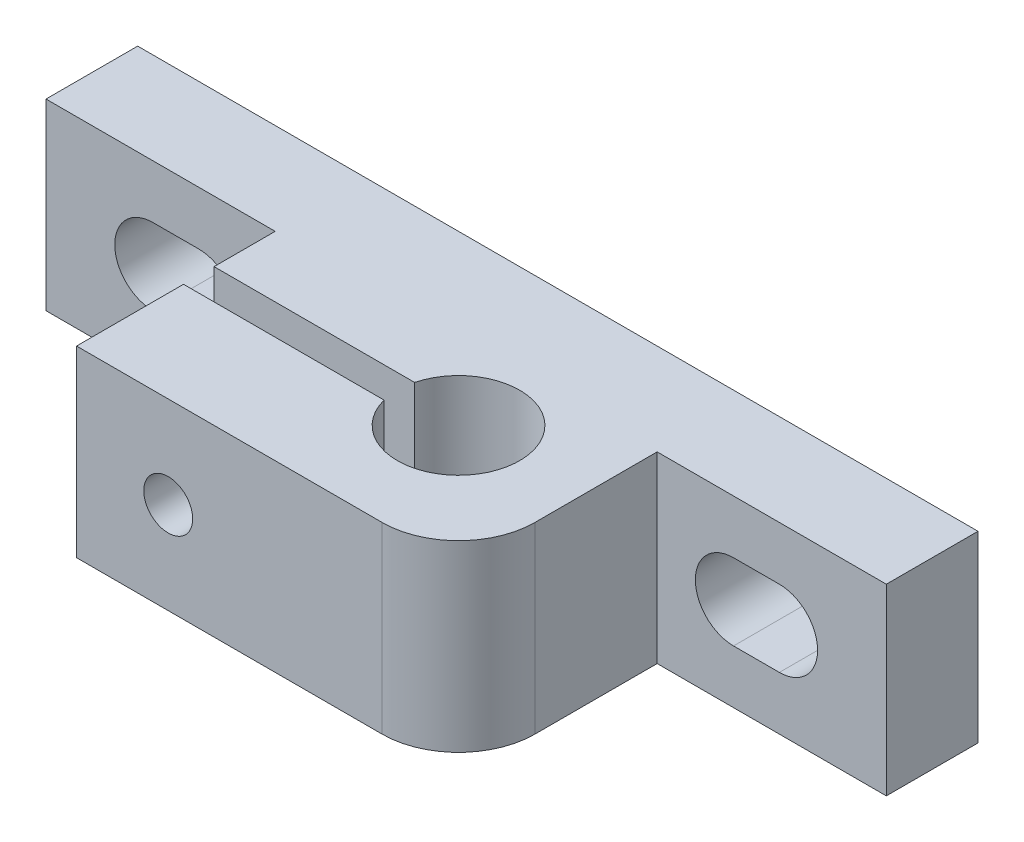
SolidWorks part; units mm, degrees
material "Copper"
ref_plane "Front Plane" through (0, 0, 0) normal (0, 0, 1) x (1, 0, 0)
ref_plane "Top Plane" through (0, 0, 0) normal (0, 1, 0) x (1, 0, 0)
ref_plane "Right Plane" through (0, 0, 0) normal (1, 0, 0) x (0, 0, -1)
sketch "Sketch2" plane through (0, 0, 0) normal (0, 0, 1) x (1, 0, 0)
  line L0 (7, 6) -> (10, 6) construction
  line L1 (0, 0) -> (55, 0)
  line L2 (0, 0) -> (0, 12)
  line L3 (0, 12) -> (55, 12)
  line L4 (55, 0) -> (55, 12)
  line L5 (27.5, 12) -> (27.5, -3.75) construction
  line L6 (7, 8.5) -> (10, 8.5)
  line L7 (7, 3.5) -> (10, 3.5)
  line L8 (48, 6) -> (45, 6) construction
  line L9 (48, 8.5) -> (45, 8.5)
  line L10 (48, 3.5) -> (45, 3.5)
  arc A0 (7, 8.5) -> (7, 3.5) centre (7, 6) ccw
  arc A1 (48, 8.5) -> (48, 3.5) centre (48, 6) cw
  arc A2 (10, 3.5) -> (10, 8.5) centre (10, 6) ccw
  arc A3 (45, 3.5) -> (45, 8.5) centre (45, 6) cw
  point P11 (8.5, 6)
  point P16 (46.5, 6)
  dimension "D1" = 7
  dimension "D2" = 3
  dimension "D5" = 55
extrude "Boss-Extrude1" add sketch "Sketch2" along normal blind 6
sketch "Sketch3" plane through (0, 0, 6) normal (0, 0, 1) x (1, 0, 0)
  line L0 (0, 0) -> (55, 0) construction
  line L1 (15, 0) -> (40, 0)
  line L2 (15, 0) -> (15, 12)
  line L3 (15, 12) -> (40, 12)
  line L4 (40, 0) -> (40, 12)
  line L5 (55, 12) -> (0, 12) construction
  line L6 (0, 12) -> (0, 0) construction
  line L7 (55, 0) -> (55, 12) construction
  dimension "D1" = 25
  dimension "D2" = 15
  dimension "D3" = 15
extrude "Boss-Extrude2" add sketch "Sketch3" along normal blind 13
fillet "Fillet1" radius 5 1 edges at (40, 6, 19)
sketch "Sketch4" plane through (0, 0, 0) normal (0, -1, 0) x (1, 0, 0)
  line L0 (15, 19) -> (35, 19) construction
  line L1 (40, 14) -> (40, 6) construction
  line L2 (0, 0) -> (55, 0) construction
  line L3 (28.127, 12) -> (15, 12)
  line L4 (15, 19) -> (15, 6) construction
  line L5 (15, 12) -> (15, 10)
  line L6 (15, 10) -> (28.127, 10)
  circle A0 centre (32, 11) radius 4
  line M4 (15, 19) -> (15, 6)
  dimension "D1" = 8
  dimension "D5" = 8
  dimension "D7" = 11
  dimension "D2" = 8
  dimension "D3" = 11
  dimension "D4" = 1
  dimension "D6" = 1
extrude "Cut-Extrude2" cut sketch "Sketch4" against normal blind 30 contours A0 L3 L6 M4 | A0 region at (21.5211, 0, 11) region at (32, 0, 11)
sketch "Sketch5" plane through (0, 0, 0) normal (0, 0, -1) x (-1, 0, 0)
  line L0 (-55, 12) -> (0, 12) construction
  line L1 (-37.6724, 9.5) -> (-17.1585, 9.5)
  line L2 (-37.6724, 9.5) -> (-37.6724, 2.5)
  line L3 (-37.6724, 2.5) -> (-17.1585, 2.5)
  line L4 (-17.1585, 9.5) -> (-17.1585, 2.5)
  line L5 (0, 0) -> (-55, 0) construction
  line L6 (0, 12) -> (0, 0) construction
  dimension "D1" = 20.5139
  dimension "D2" = 2.5
  dimension "D3" = 2.5
  dimension "D4" = 17.1585
extrude "Cut-Extrude3" cut sketch "Sketch5" against normal blind 5
sketch "Sketch6" plane through (0, 0, 19) normal (0, 0, 1) x (1, 0, 0)
  line L0 (15, 12) -> (15, 0) construction
  line L1 (35, 12) -> (15, 12) construction
  line L2 (15, 0) -> (35, 0) construction
  circle A0 centre (21, 6) radius 1.6
  dimension "D1" = 6
  dimension "D2" = 6
  dimension "D3" = 6
extrude "Cut-Extrude4" cut sketch "Sketch6" against normal blind 20
sketch "Sketch7" plane through (0, 0, 5) normal (0, 0, -1) x (-1, 0, 0)
  line L1 (-17.5359, 6) -> (-19.2679, 9)
  line L2 (-19.2679, 9) -> (-22.7321, 9)
  line L3 (-22.7321, 9) -> (-24.4641, 6)
  line L4 (-24.4641, 6) -> (-22.7321, 3)
  line L5 (-22.7321, 3) -> (-19.2679, 3)
  line L6 (-19.2679, 3) -> (-17.5359, 6)
  circle A0 centre (-21, 6) radius 3 construction
extrude "Cut-Extrude5" cut sketch "Sketch7" against normal blind 3
